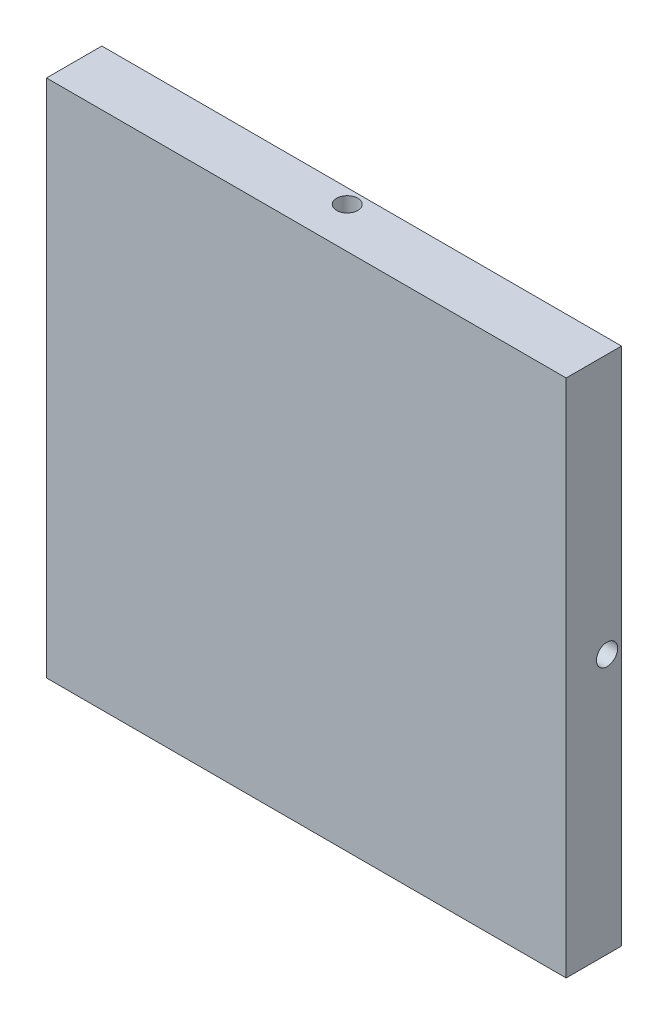
SolidWorks part; units mm, degrees
ref_plane "Front Plane" through (0, 0, 0) normal (0, 0, 1) x (1, 0, 0)
ref_plane "Top Plane" through (0, 0, 0) normal (0, 1, 0) x (1, 0, 0)
ref_plane "Right Plane" through (0, 0, 0) normal (1, 0, 0) x (0, 0, -1)
sketch "Sketch1" plane through (0, 0, 0) normal (0, 0, 1) x (1, 0, 0)
  line L1 (-85.725, 85.725) -> (85.725, 85.725)
  line L2 (-85.725, 85.725) -> (-85.725, -85.725)
  line L3 (-85.725, -85.725) -> (85.725, -85.725)
  line L4 (85.725, 85.725) -> (85.725, -85.725)
  line L5 (0, 0) -> (0, -76.9938) construction
  line L6 (-27.4443, 76.9938) -> (31.5245, 76.9938) construction
  circle A0 centre (0, 0) radius 76.9938
  circle A2 centre (0, 0) radius 3.3
  circle A5 centre (-73.025, 73.025) radius 3.175
  circle A6 centre (73.025, 73.025) radius 3.175
  circle A7 centre (73.025, -73.025) radius 3.175
  circle A8 centre (-73.025, -73.025) radius 3.175
  circle A9 centre (0, 25.4) radius 1.543
  point P12 (0, 85.725)
  point P18 (0, 0)
  point P23 (-85.725, 0)
  point P29 (0, 0)
  dimension "D1" = 153.9875
  dimension "D5" = 6.6
  dimension "D7" = 6.35
  dimension "D2" = 3.0861
  dimension "D3" = 25.4
  dimension "D8" = 12.7
  dimension "D9" = 90
  dimension "D10" = 12.7
  dimension "D11" = 4
  dimension "D12" = 85.725
  dimension "D13" = 8.7312
extrude "Boss-Extrude1" add sketch "Sketch1" along normal blind 8.7312 contours L4 L1 L2 L3 A8 A7 A6 A5 A0 | A6 | A5 | A8 | A7 | A0 A2 | A2 region at (0, 83.3003, 0) region at (-74.816, 0, 0) region at (0, 0, 0) region at (-73.025, 73.025, 0) region at (73.025, 73.025, 0) region at (73.025, -73.025, 0) region at (-73.025, -73.025, 0)
extrude "Boss-Extrude2" add sketch "Sketch1<3>" against normal blind 9.525 contours L4 L1 L2 L3 A8 A7 A6 A5 A0 | A2 region at (0, 83.3003, 0) region at (0, 0, 0)
sketch "Sketch1<3>" plane through (0, 0, 0) normal (0, 0, 1) x (1, 0, 0) same geometry as "Sketch1"
extrude "Boss-Extrude3" add sketch "Sketch1<4>" against normal blind 18.3515 contours A2 region at (0, 0, 0)
sketch "Sketch1<4>" plane through (0, 0, 0) normal (0, 0, 1) x (1, 0, 0) same geometry as "Sketch1"
sketch "Sketch2" plane through (0, 85.725, 0) normal (0, 1, 0) x (1, 0, 0)
  line L0 (-85.725, 9.525) -> (85.725, 9.525) construction
  circle A0 centre (0, 4.7625) radius 3.5
  dimension "D1" = 7
  dimension "D2" = 4.7625
extrude "Cut-Extrude1" cut sketch "Sketch2" against normal up to next
pattern_circular "CirPattern1" count 4 over 360 about axis through (0, 0, -9.525) along (0, 0, 1) of "Cut-Extrude1"
extrude "Boss-Extrude4" add sketch "Sketch1<5>" against normal blind 9.525 and the other way up to surface (8.7312 mm away) contours A9 region at (0, 25.4, 0) other way up to face at (0, 0, 8.7312)
sketch "Sketch1<5>" plane through (0, 0, 0) normal (0, 0, 1) x (1, 0, 0) same geometry as "Sketch1"
